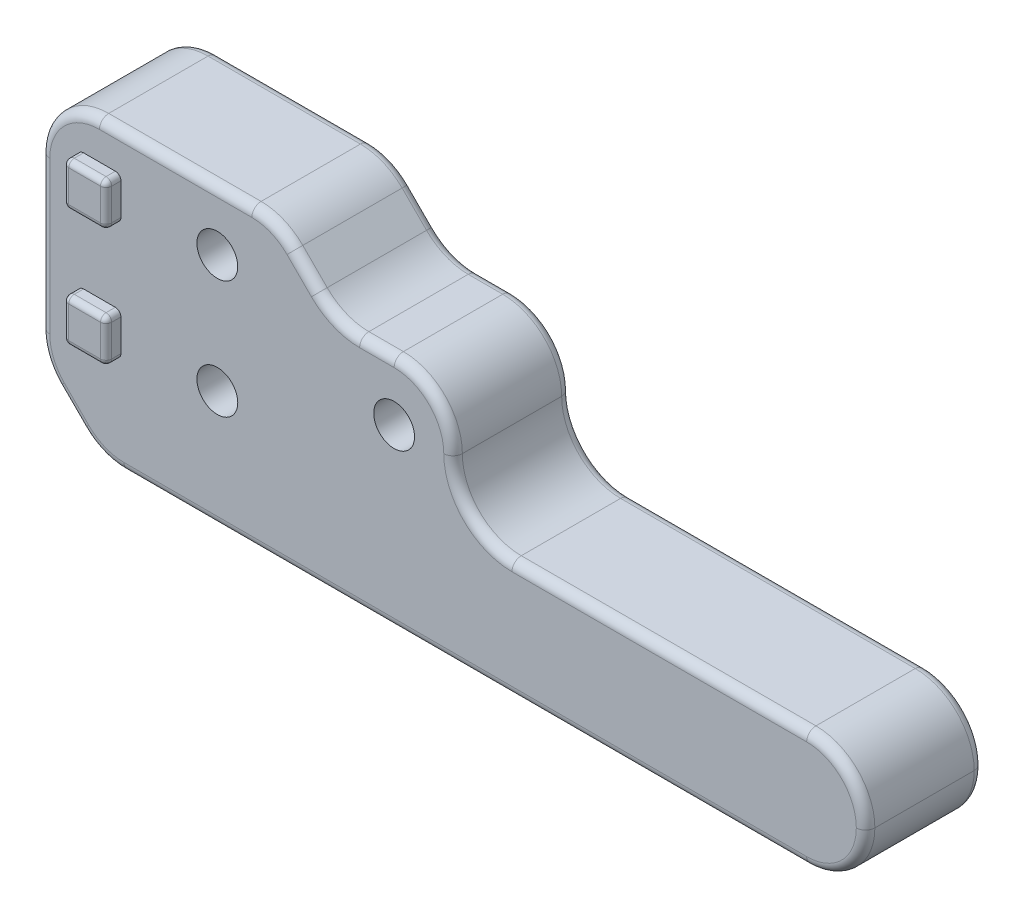
SolidWorks part; units mm, degrees
ref_plane "Front Plane" through (0, 0, 0) normal (0, 0, 1) x (1, 0, 0)
ref_plane "Top Plane" through (0, 0, 0) normal (0, 1, 0) x (1, 0, 0)
ref_plane "Right Plane" through (0, 0, 0) normal (1, 0, 0) x (0, 0, -1)
sketch "Sketch1" plane through (0, 0, 0) normal (0, 0, 1) x (1, 0, 0)
  line L0 (0, -12.7) -> (25.4, -12.7) construction
  line L1 (0, 0) -> (25.4, 0)
  line L2 (0, 0) -> (0, -25.4)
  line L3 (0, -25.4) -> (25.4, -25.4)
  line L4 (25.4, 0) -> (25.4, -25.4)
  line L5 (25.4, 0) -> (31.75, -6.35)
  line L6 (31.75, -6.35) -> (44.45, -6.35)
  line L7 (44.45, -6.35) -> (44.45, -19.05)
  line L8 (44.45, -19.05) -> (76.2, -19.05)
  line L9 (76.2, -19.05) -> (76.2, -31.75)
  line L10 (76.2, -31.75) -> (6.35, -31.75)
  line L11 (6.35, -31.75) -> (0, -25.4)
  line L13 (76.2, -19.05) -> (88.9, -19.05)
  line L14 (76.2, -19.05) -> (76.2, -31.75)
  line L15 (76.2, -31.75) -> (88.9, -31.75)
  line L16 (88.9, -19.05) -> (88.9, -31.75)
  line L17 (4.0386, -4.0386) -> (8.6614, -4.0386)
  line L18 (4.0386, -4.0386) -> (4.0386, -8.6614)
  line L19 (4.0386, -8.6614) -> (8.6614, -8.6614)
  line L20 (8.6614, -4.0386) -> (8.6614, -8.6614)
  line L21 (4.0386, -4.0386) -> (8.6614, -8.6614) construction
  line L22 (4.0386, -8.6614) -> (8.6614, -4.0386) construction
  line L23 (4.0386, -16.7386) -> (8.6614, -16.7386)
  line L24 (4.0386, -16.7386) -> (4.0386, -21.3614)
  line L25 (4.0386, -21.3614) -> (8.6614, -21.3614)
  line L26 (8.6614, -16.7386) -> (8.6614, -21.3614)
  line L27 (4.0386, -16.7386) -> (8.6614, -21.3614) construction
  line L28 (4.0386, -21.3614) -> (8.6614, -16.7386) construction
  circle A0 centre (19.05, -6.35) radius 2.2
  circle A1 centre (19.05, -19.05) radius 2.2
  circle A2 centre (38.1, -12.7) radius 2.2
  point P6 (0, -12.7)
  point P22 (6.35, -6.35)
  point P27 (6.35, -19.05)
  point P32 (0, 0)
  point P33 (0, 0)
  point P34 (0, 0)
  point P35 (0, 0)
  point P36 (0, 0)
  dimension "D11" = 4.4
  dimension "D1" = 25.4
  dimension "D2" = 25.4
  dimension "D3" = 6.35
  dimension "D4" = 45
  dimension "D5" = 12.7
  dimension "D6" = 6.35
  dimension "D7" = 45
  dimension "D8" = 12.7
  dimension "D9" = 76.2
  dimension "D10" = 12.7
  dimension "D12" = 6.35
  dimension "D13" = 6.35
  dimension "D14" = 4.6228
  dimension "D15" = 6.35
extrude "Boss-Extrude1" add sketch "Sketch1" along normal blind 12.7 contours L11 L10 L9 L8 L7 L6 L5 L4 L3 A2 | L4 L1 L2 L3 A1 A0 L17 L20 L19 L18 L23 L26 L25 L24 | L26 L23 L24 L25 | L20 L17 L18 L19 | L16 L13 L9 L15 region at (12.8369, -12.7, 0) region at (41.8174, -22.613, 0) region at (82.55, -25.4, 0) region at (6.35, -6.35, 0) region at (6.35, -19.05, 0)
extrude "Boss-Extrude2" add sketch "Sketch1<3>" along normal blind 1.6 from surface contours L20 L17 L18 L19 | L26 L23 L24 L25 region at (6.35, -6.35, 0) region at (6.35, -19.05, 0) starting at face at (40.3, -12.7, 12.7)
sketch "Sketch1<3>" plane through (0, 0, 0) normal (0, 0, 1) x (1, 0, 0) same geometry as "Sketch1"
fillet "Fillet1" radius 6.35 9 edges at (88.9, -31.75, 6.35) (88.9, -19.05, 6.35) (44.45, -19.05, 6.35) (44.45, -6.35, 6.35) (31.75, -6.35, 6.35) (25.4, 0, 6.35) (6.35, -31.75, 6.35) (0, -25.4, 6.35) (0, 0, 6.35)
fillet "Fillet2" radius 0.6 16 edges at (4.0386, -6.35, 14.3) (6.35, -4.0386, 14.3) (8.6614, -6.35, 14.3) (6.35, -8.6614, 14.3) (4.0386, -19.05, 14.3) (6.35, -16.7386, 14.3) (8.6614, -19.05, 14.3) (6.35, -21.3614, 14.3) (4.0386, -16.7386, 13.5) (8.6614, -16.7386, 13.5) (8.6614, -21.3614, 13.5) (4.0386, -21.3614, 13.5) (4.0386, -8.6614, 13.5) (8.6614, -8.6614, 13.5) (8.6614, -4.0386, 13.5) (4.0386, -4.0386, 13.5)
fillet "Fillet3" radius 1 32 edges at (1.8599, -1.8599, 0) (0, -14.5599, 0) (0.4834, -25.1998, 0) (3.175, -28.575, 0) (6.5502, -31.2666, 0) (45.7651, -31.75, 0) (87.0401, -29.8901, 0) (87.0401, -20.9099, 0) (66.675, -19.05, 0) (46.3099, -17.1901, 0) (42.5901, -8.2099, 0) (36.2401, -6.35, 0) (31.9502, -5.8666, 0) (28.575, -3.175, 0) (25.1998, -0.4834, 0) (46.3099, -17.1901, 12.7) (42.5901, -8.2099, 12.7) (36.2401, -6.35, 12.7) (31.9502, -5.8666, 12.7) (28.575, -3.175, 12.7) (25.1998, -0.4834, 12.7) (14.5599, 0, 12.7) (1.8599, -1.8599, 12.7) (0, -14.5599, 12.7) (0.4834, -25.1998, 12.7) (3.175, -28.575, 12.7) (6.5502, -31.2666, 12.7) (45.7651, -31.75, 12.7) (87.0401, -29.8901, 12.7) (87.0401, -20.9099, 12.7) (14.5599, 0, 0) (66.675, -19.05, 12.7)
